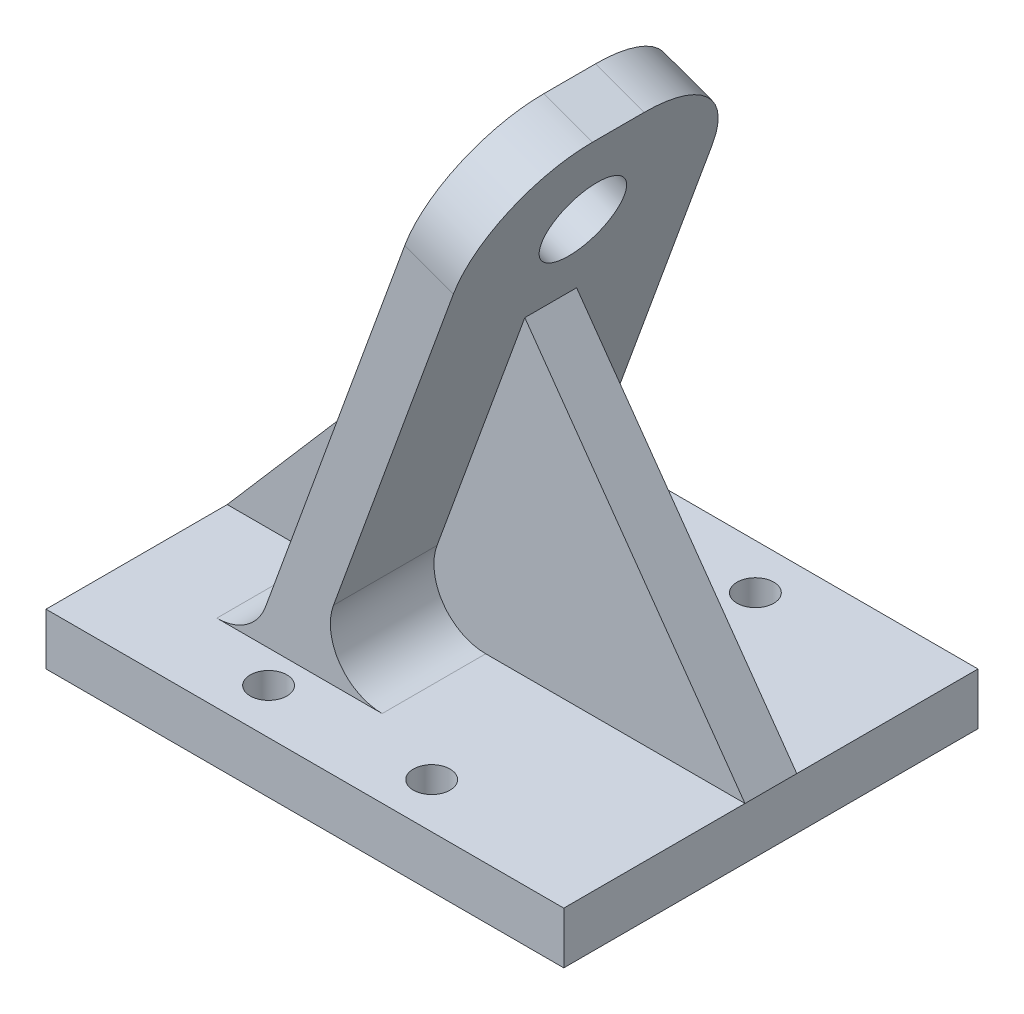
SolidWorks part; units mm, degrees
material "PLA Black"
ref_plane "Front Plane" through (0, 0, 0) normal (0, 0, 1) x (1, 0, 0)
ref_plane "Top Plane" through (0, 0, 0) normal (0, 1, 0) x (1, 0, 0)
ref_plane "Right Plane" through (0, 0, 0) normal (1, 0, 0) x (0, 0, -1)
sketch "Sketch1" plane through (0, 0, 0) normal (0, 1, 0) x (1, 0, 0)
  line L1 (-31.75, -25.4) -> (31.75, -25.4)
  line L2 (-31.75, -25.4) -> (-31.75, 25.4)
  line L3 (-31.75, 25.4) -> (31.75, 25.4)
  line L4 (31.75, -25.4) -> (31.75, 25.4)
  line L5 (-31.75, -25.4) -> (31.75, 25.4) construction
  line L6 (-31.75, 25.4) -> (31.75, -25.4) construction
  point P0 (0, 0)
  dimension "D1" = 63.5
  dimension "D2" = 50.8
extrude "Boss-Extrude1" add sketch "Sketch1" along normal blind 6.35
sketch "Sketch2" plane through (0, 0, 0) normal (0, 0, 1) x (1, 0, 0)
  line L0 (-11.43, 0) -> (13.0366, 67.2214)
  line L1 (-11.43, 0) -> (-17.397, 2.1718)
  line L2 (13.0366, 67.2214) -> (7.0695, 69.3932)
  line L3 (-17.397, 2.1718) -> (7.0695, 69.3932)
  line L4 (-11.43, 0) -> (7.0695, 69.3932) construction
  line L5 (13.0366, 67.2214) -> (-17.397, 2.1718) construction
  line L6 (31.75, 6.35) -> (31.75, 0) construction
  line L7 (-31.75, 0) -> (31.75, 0) construction
  point P1 (-2.1802, 34.6966)
  dimension "D1" = 20
  dimension "D2" = 50.8
  dimension "D3" = 11.43
extrude "Boss-Extrude2" add sketch "Sketch2" against normal mid plane 31.75
fillet "Fillet1" radius 12.7 2 edges at (10.0531, 68.3073, 15.875) (10.0531, 68.3073, -15.875)
sketch "Sketch5" plane through (-16.06, 5.8454, 0) normal (-0.9397, 0.342, 0) x (0, 0, 1)
  line L0 (-3.175, 67.6262) -> (3.175, 67.6262) construction
  circle A0 centre (0, 54.9262) radius 5.08
  point P6 (0, 67.6262)
  dimension "D1" = 10.16
  dimension "D2" = 12.7
fillet "Fillet2" radius 6.35 2 edges at (-15.8763, 6.35, 0) (-9.1188, 6.35, 0)
sketch "Sketch7" plane through (0, 0, 0) normal (0, 0, 1) x (1, 0, 0)
  line L0 (4.7485, 44.45) -> (31.75, 6.35)
  line L2 (-31.75, 6.35) -> (31.75, 6.35) construction
  line L3 (-31.75, 6.35) -> (-20.3226, 6.35)
  line L7 (-31.75, 6.35) -> (-4.3203, 38.1)
  line L8 (2.7259, 57.4591) -> (-14.3556, 10.5282) construction
  line L10 (-4.3203, 38.1) -> (-14.3556, 10.5282)
  line L12 (-0.05, 6.35) -> (31.75, 6.35)
  line L13 (-6.0171, 14.8718) -> (4.7485, 44.45)
  line L14 (-6.0171, 14.8718) -> (8.6929, 55.2873) construction
  arc A0 (-6.0171, 14.8718) -> (-0.05, 6.35) centre (-0.05, 12.7) ccw construction
  arc A4 (-20.3226, 6.35) -> (-14.3556, 10.5282) centre (-20.3226, 12.7) ccw construction
  arc A5 (-6.0171, 14.8718) -> (-0.05, 6.35) centre (-0.05, 12.7) ccw
  arc A6 (-20.3226, 6.35) -> (-14.3556, 10.5282) centre (-20.3226, 12.7) ccw
  dimension "D1" = 31.75
  dimension "D2" = 38.1
extrude "Boss-Extrude5" add sketch "Sketch7" along normal mid plane 6.35
extrude "Cut-Extrude3" cut sketch "Sketch5" against normal through all
sketch "Sketch8" plane through (0, 6.35, 0) normal (0, 1, 0) x (1, 0, 0)
  line L4 (-10, -19.85) -> (10, 19.85) construction
  circle A0 centre (10, -19.85) radius 2.25
  circle A1 centre (10, 19.85) radius 2.25
  circle A2 centre (-10, 19.85) radius 2.25
  circle A3 centre (-10, -19.85) radius 2.25
  point P8 (0, 0)
  dimension "D2" = 4.5
  dimension "D1" = 39.7
  dimension "D5" = 20
extrude "Cut-Extrude4" cut sketch "Sketch8" against normal through all
